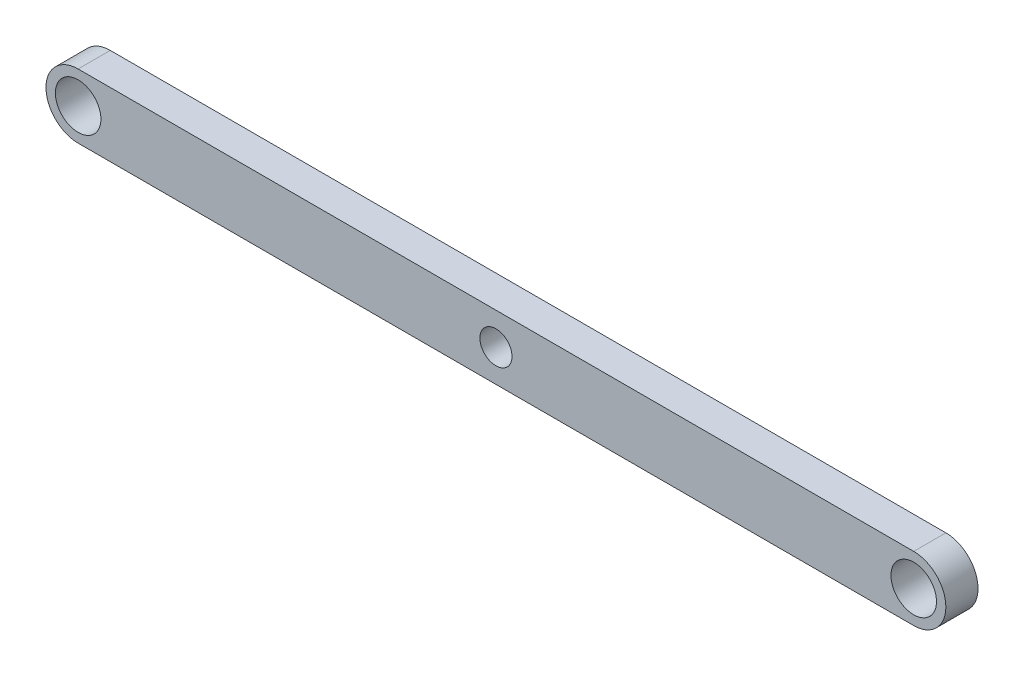
SolidWorks part; units mm, degrees
ref_plane "Front Plane" through (0, 0, 0) normal (0, 0, 1) x (1, 0, 0)
ref_plane "Top Plane" through (0, 0, 0) normal (0, 1, 0) x (1, 0, 0)
ref_plane "Right Plane" through (0, 0, 0) normal (1, 0, 0) x (0, 0, -1)
sketch "Sketch1" plane through (0, 0, 0) normal (0, 0, 1) x (1, 0, 0)
  line L0 (-82.55, 0) -> (82.55, 0) construction
  line L1 (-82.55, 6.35) -> (82.55, 6.35)
  line L2 (-82.55, -6.35) -> (82.55, -6.35)
  arc A0 (-82.55, 6.35) -> (-82.55, -6.35) centre (-82.55, 0) ccw
  arc A1 (82.55, -6.35) -> (82.55, 6.35) centre (82.55, 0) ccw
  circle A2 centre (-82.55, 0) radius 4.5
  circle A3 centre (82.55, 0) radius 4.5
  circle A4 centre (0, 0) radius 3.175
  point P2 (0, 0)
  dimension "D3" = 9
  dimension "D4" = 6.35
  dimension "D1" = 165.1
  dimension "D2" = 12.7
extrude "Boss-Extrude1" add sketch "Sketch1" along normal blind 6.35
